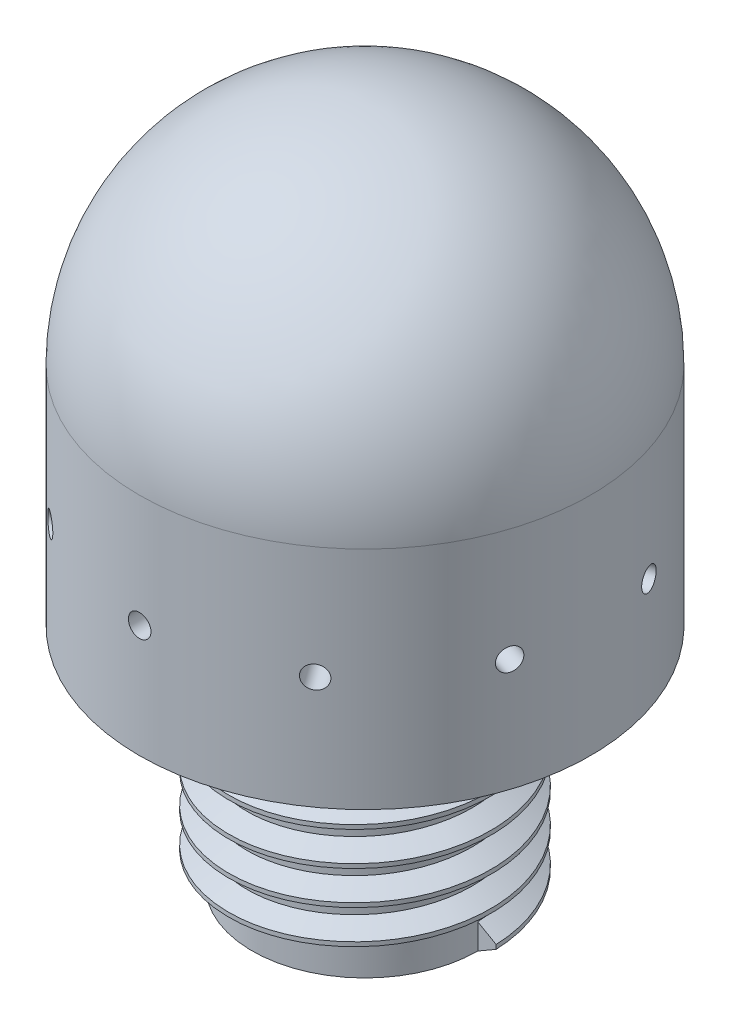
SolidWorks part; units mm, degrees
ref_plane "Front Plane" through (0, 0, 0) normal (0, 0, 1) x (1, 0, 0)
ref_plane "Top Plane" through (0, 0, 0) normal (0, 1, 0) x (1, 0, 0)
ref_plane "Right Plane" through (0, 0, 0) normal (1, 0, 0) x (0, 0, -1)
sketch "Sketch2" plane through (0, 0, 0) normal (0, 1, 0) x (1, 0, 0)
  circle A0 centre (0, 0) radius 10
extrude "Boss-Extrude1" add sketch "Sketch2" along normal blind 20
fillet "Fillet1" radius 10 1 edges at (0, 20, 10)
sketch "Sketch3" plane through (0, 0, 0) normal (0, -1, 0) x (1, 0, 0)
  circle A0 centre (0, 0) radius 5
extrude "Boss-Extrude2" add sketch "Sketch3" along normal blind 10 contours A0
sketch "Sketch4" plane through (0, -10, 0) normal (0, -1, 0) x (1, 0, 0)
  circle A0 centre (0, 0) radius 2
extrude "Cut-Extrude1" cut sketch "Sketch4" against normal blind 20 contours A0
ref_plane "Plane1" through (0, 0, 10) normal (0, 0, -1) x (-1, 0, 0)
sketch "Sketch5" plane through (0, 0, 10) normal (0, 0, -1) x (-1, 0, 0)
  line L0 (-5, 0) -> (5, 0) construction
  circle A0 centre (0, 5) radius 0.5
  dimension "D1" = 5
extrude "Cut-Extrude2" cut sketch "Sketch5" along normal up to next
pattern_circular "CirPattern1" count 10 over 360 about axis through (0, 20, 0) along (0, -1, 0) of "Cut-Extrude2" reverse direction yes
thread "Thread1" pitch 1.5 method extrude profile "Thread Profile1" start angle 0, offset 0, length 0, pitch 1.5, diameter 10
ref_plane "Plane2" through (5, -10, 0) normal (0, 0, 1) x (1, 0, 0)
sketch "Thread Profile1" plane through (5, -10, 0) normal (0, 0, 1) x (1, 0, 0)
  line L0 (0, 0) -> (0, 1.5) construction
  line L1 (0, 0) -> (0.8119, 0.4687)
  line L2 (0.8119, 0.4687) -> (0.8119, 0.6562)
  line L3 (0.8119, 0.6562) -> (0, 1.125)
  line L4 (0.8119, 0.5625) -> (0, 0.5625) construction
  line L11 (0, 0) -> (0, 1.125)
  point P2 (0, 0)
  dimension "Pitch" = 1.5
  dimension "Profile_Angle" = 60
  dimension "Profile_Land" = 0.1875
  dimension "Profile_Height" = 0.8119
